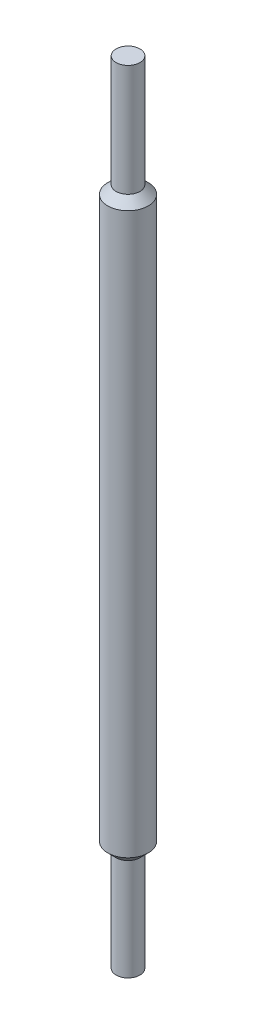
SolidWorks part; units mm, degrees
ref_plane "Front Plane" through (0, 0, 0) normal (0, 0, 1) x (1, 0, 0)
ref_plane "Top Plane" through (0, 0, 0) normal (0, 1, 0) x (1, 0, 0)
ref_plane "Right Plane" through (0, 0, 0) normal (1, 0, 0) x (0, 0, -1)
sketch "Sketch1" plane through (0, 0, 0) normal (0, 1, 0) x (1, 0, 0)
  circle A0 centre (0, 0) radius 6.35
  dimension "D1" = 12.7
extrude "Boss-Extrude1" add sketch "Sketch1" along normal blind 421.64
sketch "Sketch2" plane through (0, 0, 0) normal (0, -1, 0) x (-1, 0, 0)
  circle A0 centre (0, 0) radius 10.795
  dimension "D1" = 21.59
extrude "Boss-Extrude2" add sketch "Sketch2" against normal blind 421.64
sketch "Sketch3" plane through (0, 0, 0) normal (0, -1, 0) x (1, 0, 0)
  circle A0 centre (0, 0) radius 6.35
  circle A1 centre (0, 0) radius 25.4
  dimension "D1" = 12.7
  dimension "D2" = 50.8
extrude "Cut-Extrude1" cut sketch "Sketch3" against normal blind 52.324
sketch "Sketch4" plane through (0, 421.64, 0) normal (0, 1, 0) x (1, 0, 0)
  circle A0 centre (0, 0) radius 6.35
  circle A1 centre (0, 0) radius 25.4
  dimension "D1" = 50.8
  dimension "D2" = 12.7
extrude "Cut-Extrude2" cut sketch "Sketch4" against normal blind 57.658
ref_plane "Plane1" through (0, 210.82, 0) normal (0, 1, 0) x (1, 0, 0)
sketch "Sketch5" plane through (0, 210.82, 0) normal (0, 1, 0) x (1, 0, 0)
  circle A0 centre (0, 0) radius 15.875
  dimension "D1" = 31.75
chamfer "Chamfer1" distance 6.35 angle 45 2 edges at (0, 52.324, -10.795) (0, 363.982, 10.795)
